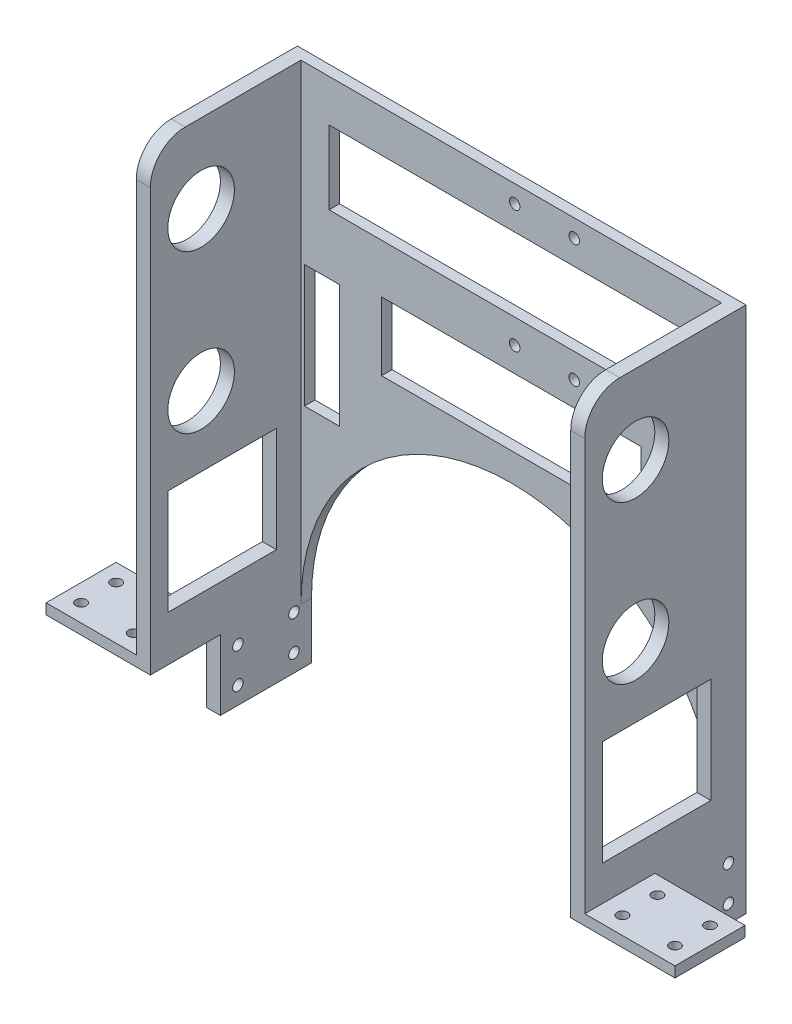
SolidWorks part; units mm, degrees
material "1060 合金"
ref_plane "前视基准面" through (0, 0, 0) normal (0, 0, 1) x (1, 0, 0)
ref_plane "上视基准面" through (0, 0, 0) normal (0, 1, 0) x (1, 0, 0)
ref_plane "右视基准面" through (0, 0, 0) normal (1, 0, 0) x (0, 0, -1)
sketch "草图1" plane through (0, 0, 0) normal (0, 0, 1) x (1, 0, 0)
  line L1 (-80, 78.75) -> (80, 78.75)
  line L2 (-80, 78.75) -> (-80, -78.75)
  line L3 (-80, -78.75) -> (80, -78.75)
  line L4 (80, 78.75) -> (80, -78.75)
  line L5 (-80, 78.75) -> (80, -78.75) construction
  line L6 (-80, -78.75) -> (80, 78.75) construction
  point P0 (0, 0)
  dimension "D1" = 157.5
  dimension "D2" = 160
extrude "凸台-拉伸1" add sketch "草图1" along normal blind 46
sketch "草图2" plane through (0, 0, 46) normal (0, 0, 1) x (1, 0, 0)
  line L1 (-60, 78.75) -> (60, 78.75)
  line L2 (-60, 78.75) -> (-60, -78.75)
  line L3 (-60, -78.75) -> (60, -78.75)
  line L4 (60, 78.75) -> (60, -78.75)
  line L5 (-60, 78.75) -> (60, -78.75) construction
  line L6 (-60, -78.75) -> (60, 78.75) construction
  line L7 (-80, -78.75) -> (80, -78.75) construction
  point P0 (0, 0)
  dimension "D1" = 157.5
  dimension "D2" = 120
extrude "切除-拉伸1" cut sketch "草图2" against normal blind 43
sketch "草图3" plane through (0, 0, 46) normal (0, 0, 1) x (1, 0, 0)
  line L1 (-80, 78.75) -> (-64, 78.75)
  line L2 (-80, 78.75) -> (-80, -76.25)
  line L3 (-80, -76.25) -> (-64, -76.25)
  line L4 (-64, 78.75) -> (-64, -76.25)
  line L5 (80, 78.75) -> (64, 78.75)
  line L6 (80, 78.75) -> (80, -76.25)
  line L7 (80, -76.25) -> (64, -76.25)
  line L8 (64, 78.75) -> (64, -76.25)
  dimension "D1" = 155
  dimension "D2" = 16
  dimension "D3" = 155
  dimension "D4" = 16
extrude "切除-拉伸2" cut sketch "草图3" against normal through all
sketch "草图4" plane through (-64, 0, 0) normal (-1, 0, 0) x (0, 0, 1)
  line L0 (46, -76.25) -> (46, 78.75) construction
  line L1 (46, -78.75) -> (0, -78.75) construction
  circle A0 centre (31.5, -15.75) radius 9.5
  dimension "D1" = 19
  dimension "D2" = 14.5
  dimension "D3" = 63
extrude "切除-拉伸3" cut sketch "草图4" against normal through all
sketch "草图5" plane through (64, 0, 0) normal (1, 0, 0) x (0, 0, -1)
  line L0 (-46, 78.75) -> (-46, -76.25) construction
  circle A0 centre (-31.5, 29.25) radius 9.5
  circle A1 centre (-31.5, -15.75) radius 9.5 construction
  dimension "D1" = 19
  dimension "D2" = 14.5
  dimension "D3" = 45
extrude "切除-拉伸4" cut sketch "草图5" against normal through all
sketch "草图7" plane through (0, 0, 3) normal (0, 0, 1) x (1, 0, 0)
  line L1 (60, 78.75) -> (-60, 78.75) construction
  line L2 (60, -78.75) -> (60, 78.75) construction
  circle A0 centre (1, 46.75) radius 1.5
  circle A1 centre (18, 46.75) radius 1.5
  circle A2 centre (1, 11.75) radius 1.5
  circle A3 centre (18, 11.75) radius 1.5
  dimension "D1" = 3
  dimension "D2" = 3
  dimension "D3" = 3
  dimension "D4" = 3
  dimension "D5" = 32
  dimension "D6" = 17
  dimension "D7" = 35
  dimension "D8" = 17
  dimension "D9" = 35
  dimension "D10" = 59
  dimension "D11" = 32
  dimension "D12" = 42
extrude "切除-拉伸6" cut sketch "草图7" against normal blind 10
sketch "草图10" plane through (0, -76.25, 0) normal (0, 1, 0) x (1, 0, 0)
  line L0 (-64, 0) -> (-64, -46) construction
  line L1 (-80, 0) -> (-64, 0)
  line L2 (-80, 0) -> (-80, -26)
  line L3 (-80, -26) -> (-64, -26)
  line L4 (-64, 0) -> (-64, -26)
  line L5 (64, 0) -> (64, -46) construction
  line L6 (80, 0) -> (64, 0)
  line L7 (80, 0) -> (80, -26)
  line L8 (80, -26) -> (64, -26)
  line L9 (64, 0) -> (64, -26)
  dimension "D1" = 26
  dimension "D2" = 26
extrude "切除-拉伸9" cut sketch "草图10" against normal blind 10
sketch "草图11" plane through (0, -78.75, 0) normal (0, -1, 0) x (1, 0, 0)
  line L1 (-64, 0) -> (-60, 0)
  line L2 (-64, 0) -> (-64, 26)
  line L3 (-64, 26) -> (-60, 26)
  line L4 (-60, 0) -> (-60, 26)
  line L5 (-60, 3) -> (-60, 46) construction
  line L7 (60, 0) -> (64, 0)
  line L8 (60, 0) -> (60, 26)
  line L9 (60, 26) -> (64, 26)
  line L10 (64, 0) -> (64, 26)
  line L11 (64, 0) -> (64, 26) construction
  dimension "D1" = 26
  dimension "D2" = 4
  dimension "D3" = 26
  dimension "D4" = 4
extrude "凸台-拉伸2" add sketch "草图11" along normal blind 20
sketch "草图13" plane through (-64, 0, 0) normal (-1, 0, 0) x (0, 0, 1)
  line L0 (26, -98.75) -> (0, -98.75) construction
  line L1 (5, -83.75) -> (21, -83.75) construction
  line L2 (5, -83.75) -> (5, -93.75) construction
  line L3 (5, -93.75) -> (21, -93.75) construction
  line L4 (21, -83.75) -> (21, -93.75) construction
  line L5 (5, -83.75) -> (21, -93.75) construction
  line L6 (5, -93.75) -> (21, -83.75) construction
  line L7 (26, -98.75) -> (26, -78.75) construction
  circle A0 centre (5, -83.75) radius 1.5
  circle A1 centre (21, -83.75) radius 1.5
  circle A2 centre (21, -93.75) radius 1.5
  circle A3 centre (5, -93.75) radius 1.5
  point P0 (13, -88.75)
  dimension "D5" = 3
  dimension "D6" = 3
  dimension "D7" = 3
  dimension "D8" = 3
  dimension "D1" = 10
  dimension "D2" = 5
  dimension "D3" = 5
  dimension "D4" = 16
extrude "切除-拉伸11" cut sketch "草图13" against normal through all
sketch "草图17" plane through (0, 0, 46) normal (0, 0, 1) x (1, 0, 0)
  line L1 (-60, -78.75) -> (-89.75, -78.75)
  line L2 (-60, -78.75) -> (-60, -75.75)
  line L3 (-60, -75.75) -> (-89.75, -75.75)
  line L4 (-89.75, -78.75) -> (-89.75, -75.75)
  line L5 (60, -78.75) -> (89.75, -78.75)
  line L6 (60, -78.75) -> (60, -75.75)
  line L7 (60, -75.75) -> (89.75, -75.75)
  line L8 (89.75, -78.75) -> (89.75, -75.75)
  dimension "D1" = 3
  dimension "D2" = 29.75
  dimension "D3" = 3
  dimension "D4" = 29.75
extrude "凸台-拉伸3" add sketch "草图17" against normal blind 20
sketch "草图18" plane through (0, -75.75, 0) normal (0, 1, 0) x (1, 0, 0)
  line L0 (89.75, -26) -> (89.75, -46) construction
  line L1 (-84.75, -31) -> (-69.75, -31) construction
  line L2 (-84.75, -31) -> (-84.75, -41) construction
  line L3 (-84.75, -41) -> (-69.75, -41) construction
  line L4 (-69.75, -31) -> (-69.75, -41) construction
  line L5 (-84.75, -31) -> (-69.75, -41) construction
  line L6 (-84.75, -41) -> (-69.75, -31) construction
  line L7 (69.75, -31) -> (84.75, -31) construction
  line L8 (69.75, -31) -> (69.75, -41) construction
  line L9 (69.75, -41) -> (84.75, -41) construction
  line L10 (84.75, -31) -> (84.75, -41) construction
  line L11 (69.75, -31) -> (84.75, -41) construction
  line L12 (69.75, -41) -> (84.75, -31) construction
  line L13 (-89.75, -26) -> (-89.75, -46) construction
  line L14 (-64, -46) -> (-89.75, -46) construction
  line L15 (89.75, -46) -> (64, -46) construction
  circle A0 centre (84.75, -31) radius 1.5
  circle A1 centre (84.75, -41) radius 1.5
  circle A2 centre (69.75, -31) radius 1.5
  circle A3 centre (69.75, -41) radius 1.5
  circle A4 centre (-69.75, -31) radius 1.5
  circle A5 centre (-69.75, -41) radius 1.5
  circle A6 centre (-84.75, -41) radius 1.5
  circle A7 centre (-84.75, -31) radius 1.5
  point P0 (-77.25, -36)
  point P5 (77.25, -36)
  point P12 (89.75, -36)
  dimension "D9" = 3
  dimension "D10" = 3
  dimension "D11" = 3
  dimension "D12" = 3
  dimension "D13" = 3
  dimension "D14" = 3
  dimension "D15" = 3
  dimension "D16" = 3
  dimension "D1" = 10
  dimension "D2" = 15
  dimension "D3" = 10
  dimension "D4" = 15
  dimension "D5" = 5
  dimension "D6" = 5
  dimension "D7" = 5
  dimension "D8" = 5
extrude "切除-拉伸14" cut sketch "草图18" against normal blind 20
sketch "草图19" plane through (-64, 0, 0) normal (-1, 0, 0) x (0, 0, 1)
  line L0 (46, -75.75) -> (46, 78.75) construction
  line L1 (0, 78.75) -> (46, 78.75)
  line L2 (0, 78.75) -> (0, 51.75)
  line L3 (0, 51.75) -> (46, 51.75)
  line L4 (46, 78.75) -> (46, 51.75)
  dimension "D1" = 27
extrude "切除-拉伸15" cut sketch "草图19" against normal through all
sketch "草图20" plane through (0, 0, 3) normal (0, 0, 1) x (1, 0, 0)
  circle A0 centre (0, -52.75) radius 30
  dimension "D1" = 60
extrude "切除-拉伸16" cut sketch "草图20" against normal blind 10
sketch "草图21" plane through (0, 0, 0) normal (0, 0, -1) x (-1, 0, 0)
  line L1 (60, -78.75) -> (-60, -78.75)
  line L2 (60, -78.75) -> (60, -22.75)
  line L3 (60, -22.75) -> (-60, -22.75)
  line L4 (-60, -78.75) -> (-60, -22.75)
  dimension "D1" = 56
extrude "切除-拉伸17" cut sketch "草图21" against normal blind 10
fillet "圆角1" radius 60 2 edges at (60, -22.75, 1.5) (-60, -22.75, 1.5)
sketch "草图22" plane through (0, 0, 3) normal (0, 0, 1) x (1, 0, 0)
  line L1 (49, 1.75) -> (59, 1.75)
  line L2 (49, 1.75) -> (49, -33.25)
  line L3 (49, -33.25) -> (59, -33.25)
  line L4 (59, 1.75) -> (59, -33.25)
  line L5 (49, 1.75) -> (59, -33.25) construction
  line L6 (49, -33.25) -> (59, 1.75) construction
  line L7 (60, -82.75) -> (60, 51.75) construction
  line L8 (60, -78.75) -> (89.75, -78.75) construction
  line L9 (0, 51.75) -> (0, -22.75) construction
  line L10 (-60, 51.75) -> (60, 51.75) construction
  line L11 (-49, -33.25) -> (-59, -33.25)
  line L12 (-59, 1.75) -> (-59, -33.25)
  line L13 (-49, 1.75) -> (-59, 1.75)
  line L14 (-49, 1.75) -> (-49, -33.25)
  point P0 (54, -15.75)
  dimension "D1" = 35
  dimension "D2" = 10
  dimension "D3" = 63
  dimension "D4" = 1
extrude "切除-拉伸18" cut sketch "草图22" against normal blind 10
fillet "圆角2" radius 10 2 edges at (62, 51.75, 46) (-62, 51.75, 46)
sketch "草图24" plane through (-64, 0, 0) normal (-1, 0, 0) x (0, 0, 1)
  line L0 (46, -75.75) -> (46, 41.75) construction
  line L1 (10, -35.75) -> (41, -35.75)
  line L2 (10, -35.75) -> (10, -65.75)
  line L3 (10, -65.75) -> (41, -65.75)
  line L4 (41, -35.75) -> (41, -65.75)
  line L5 (10, -35.75) -> (41, -65.75) construction
  line L6 (10, -65.75) -> (41, -35.75) construction
  line L7 (26, -75.75) -> (46, -75.75) construction
  line L8 (0, -98.75) -> (0, 51.75) construction
  circle A0 centre (31.5, -15.75) radius 9.5 construction
  point P0 (25.5, -50.75)
  dimension "D1" = 5
  dimension "D2" = 10
  dimension "D3" = 10
  dimension "D4" = 20
extrude "切除-拉伸19" cut sketch "草图24" against normal through all
sketch "草图25" plane through (0, 0, 3) normal (0, 0, 1) x (1, 0, 0)
  line L0 (-60, 51.75) -> (-60, -82.75) construction
  line L1 (-52, 39.75) -> (52, 39.75)
  line L2 (-52, 39.75) -> (-52, 18.75)
  line L3 (-52, 18.75) -> (52, 18.75)
  line L4 (52, 39.75) -> (52, 18.75)
  line L5 (-52, 39.75) -> (52, 18.75) construction
  line L6 (-52, 18.75) -> (52, 39.75) construction
  line L7 (60, -78.75) -> (60, 41.75) construction
  line L8 (-49, -33.25) -> (-49, 1.75) construction
  line L9 (-37, 4.75) -> (37, 4.75)
  line L10 (-37, 4.75) -> (-37, -14.75)
  line L11 (-37, -14.75) -> (37, -14.75)
  line L12 (37, 4.75) -> (37, -14.75)
  line L13 (-37, 4.75) -> (37, -14.75) construction
  line L14 (-37, -14.75) -> (37, 4.75) construction
  line L15 (49, 1.75) -> (49, -33.25) construction
  circle A0 centre (18, 46.75) radius 1.5 construction
  circle A1 centre (18, 11.75) radius 1.5 construction
  arc A2 (60, -82.75) -> (0, -22.75) centre (0, -82.75) ccw construction
  circle A3 centre (1, 11.75) radius 1.5 construction
  point P0 (0, 29.25)
  point P13 (0, -5)
  dimension "D1" = 8
  dimension "D2" = 8
  dimension "D3" = 7
  dimension "D4" = 7
  dimension "D5" = 12
  dimension "D6" = 12
  dimension "D7" = 68
  dimension "D8" = 7
extrude "切除-拉伸20" cut sketch "草图25" against normal blind 10
